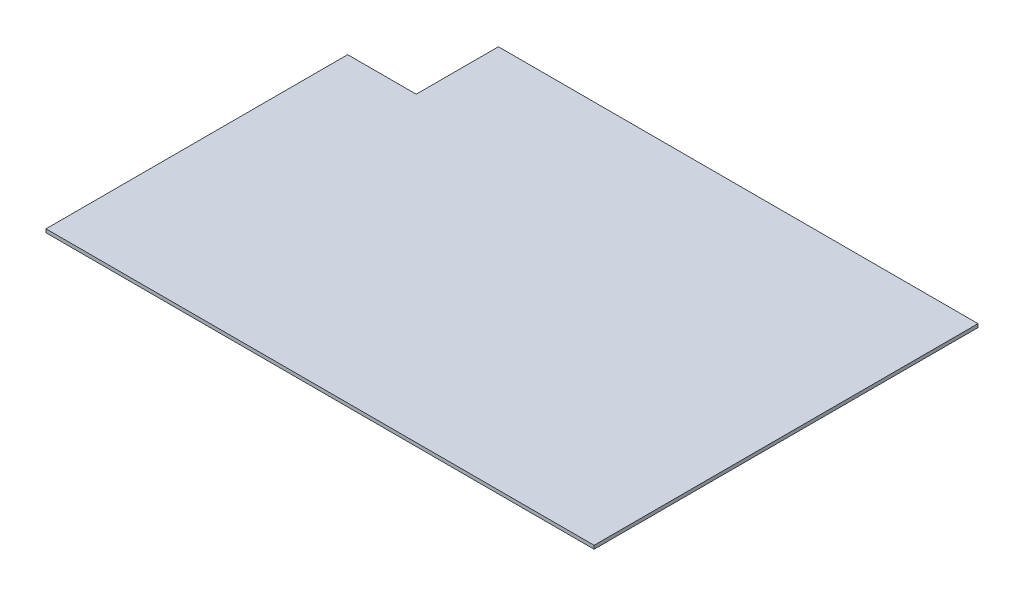
SolidWorks part; units mm, degrees
ref_plane "Front Plane" through (0, 0, 0) normal (0, 0, 1) x (1, 0, 0)
ref_plane "Top Plane" through (0, 0, 0) normal (0, 1, 0) x (1, 0, 0)
ref_plane "Right Plane" through (0, 0, 0) normal (1, 0, 0) x (0, 0, -1)
sketch "Sketch1" plane through (0, 0, 0) normal (0, 1, 0) x (1, 0, 0)
  line L0 (-130.625, 184.7613) -> (351.9808, 184.7613) construction
  line L1 (-124.2728, 0.5153) -> (129.7272, 0.5153)
  line L2 (-124.2728, 0.5153) -> (-124.2728, 140.3113)
  line L3 (-92.5228, 178.4113) -> (129.7272, 178.4113)
  line L4 (129.7272, 0.5153) -> (129.7272, 178.4113)
  line L15 (-124.2728, 140.3113) -> (-92.5228, 140.3113)
  line L16 (-92.5228, 178.4113) -> (-92.5228, 140.3113)
  line L21 (351.9786, 184.7613) -> (351.9786, -3.4747) construction
  line L22 (351.9808, -5.8347) -> (-130.625, -5.8347) construction
  line L23 (-130.6228, -5.8347) -> (-130.6228, 184.7613) construction
  point P1 (0, 0)
  dimension "D1" = 6.35
  dimension "D2" = 476.2514
  dimension "D3" = 6.35
  dimension "D4" = 254
  dimension "D5" = 6.35
  dimension "D6" = 38.1
  dimension "D7" = 31.75
extrude "Boss-Extrude1" add sketch "Sketch1" along normal blind 1.6002 contours L1 L4 L3 L2 L15 L16 region at (5.784, 0, -87.5405)
